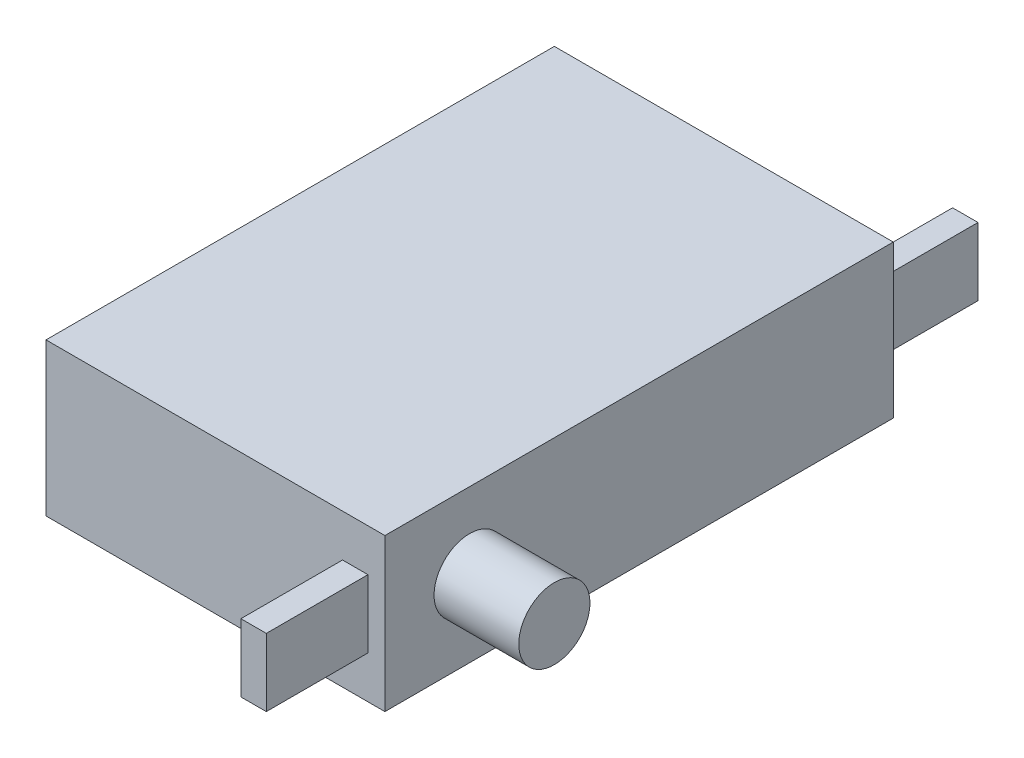
SolidWorks part; units mm, degrees
ref_plane "Front Plane" through (0, 0, 0) normal (0, 0, 1) x (1, 0, 0)
ref_plane "Top Plane" through (0, 0, 0) normal (0, 1, 0) x (1, 0, 0)
ref_plane "Right Plane" through (0, 0, 0) normal (1, 0, 0) x (0, 0, -1)
sketch "Sketch1" plane through (0, 0, 0) normal (0, 1, 0) x (1, 0, 0)
  line L1 (0, 0) -> (20, 0)
  line L2 (0, 0) -> (0, 30)
  line L3 (0, 30) -> (20, 30)
  line L4 (20, 0) -> (20, 30)
  point P4 (0, 0)
  dimension "D1" = 30
  dimension "D2" = 20
extrude "Boss-Extrude1" add sketch "Sketch1" along normal mid plane 9
sketch "Sketch2" plane through (20, 0, 0) normal (1, 0, 0) x (0, 0, -1)
  line L0 (0, 4.5) -> (0, -4.5) construction
  circle A0 centre (5, 0) radius 2.1
  point P2 (0, 0)
  dimension "D1" = 4.2
  dimension "D2" = 5
extrude "Boss-Extrude2" add sketch "Sketch2" along normal blind 5
sketch "Sketch3" plane through (0, 0, 0) normal (0, 0, 1) x (1, 0, 0)
  line L0 (20, 4.5) -> (20, -4.5) construction
  line L1 (17.5, 2) -> (19, 2)
  line L2 (17.5, 2) -> (17.5, -2)
  line L3 (17.5, -2) -> (19, -2)
  line L4 (19, 2) -> (19, -2)
  point P6 (20, 0)
  point P7 (19, 0)
  dimension "D1" = 4
  dimension "D2" = 1.5
  dimension "D3" = 1
extrude "Boss-Extrude3" add sketch "Sketch3" along normal blind 6
sketch "Sketch4" plane through (0, 0, -30) normal (0, 0, -1) x (-1, 0, 0)
  line L4 (-17.5, -2) -> (-17.5, 2)
  line L5 (-19, -2) -> (-17.5, -2)
  line L6 (-19, 2) -> (-19, -2)
  line L7 (-17.5, 2) -> (-19, 2)
  line L8 (-17.5, -2) -> (-17.5, 2)
  line L9 (-19, -2) -> (-17.5, -2)
  line L10 (-19, 2) -> (-19, -2)
  line L11 (-17.5, 2) -> (-19, 2)
  dimension "D1" = 0
extrude "Boss-Extrude4" add sketch "Sketch4" along normal blind 6
